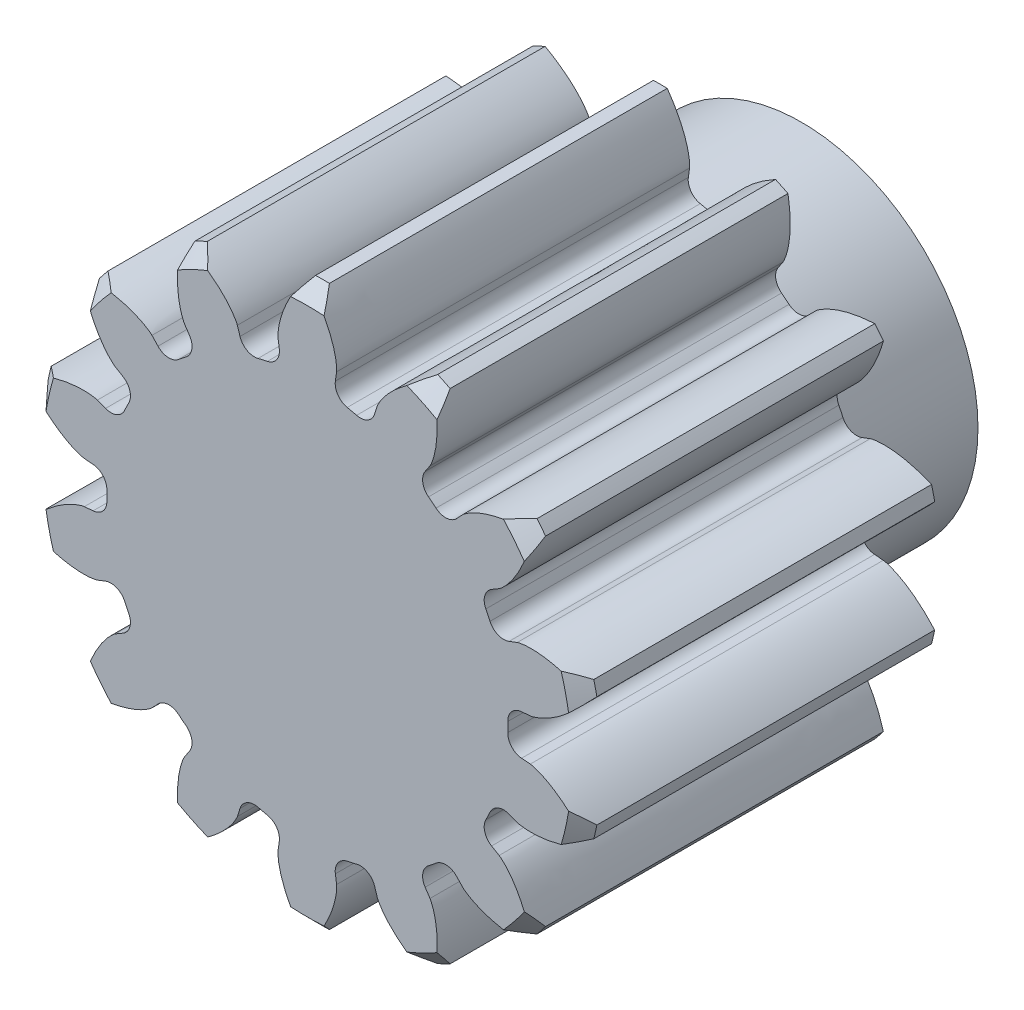
SolidWorks part; units mm, degrees
ref_plane "Front Plane" through (0, 0, 0) normal (0, 0, 1) x (1, 0, 0)
ref_plane "Top Plane" through (0, 0, 0) normal (0, 1, 0) x (1, 0, 0)
ref_plane "Right Plane" through (0, 0, 0) normal (1, 0, 0) x (0, 0, -1)
ref_axis "Axis1" through (0, 0, -5.7505) along (0, 0, 1)
sketch "Sketch1" plane through (0, 0, 0) normal (0, 0, 1) x (1, 0, 0)
  circle A0 centre (0, 0) radius 8
  dimension "D1" = 16
extrude "Boss-Extrude1" add sketch "Sketch1" along normal blind 10
sketch "Sketch2" plane through (0, 0, 10) normal (0, 0, 1) x (1, 0, 0)
  line L0 (0, 0) -> (5.7306, 0.4723) construction
  line L1 (5.7306, 0.4723) -> (6.3227, 0.5211)
  line L2 (0, 0) -> (5.7306, -0.4723) construction
  line L3 (5.7306, -0.4723) -> (6.3227, -0.5211)
  circle A0 centre (0, 0) radius 7 construction
  circle A1 centre (0, 0) radius 8 construction
  circle A2 centre (0, 0) radius 6.3442 construction
  circle A3 centre (0, 0) radius 5.75 construction
  arc A4 (5.7306, 0.4723) -> (5.7306, -0.4723) centre (0, 0) cw
  arc A5 (7.8478, 1.5531) -> (7.8478, -1.5531) centre (0, 0) cw
  spline S0 degree 4 poles (6.3227, 0.5211) (6.3255, 0.5213) (6.3332, 0.5222) (6.3477, 0.5245) (6.3713, 0.5289) (6.4148, 0.5388) (6.4666, 0.5535) (6.5244, 0.5726) (6.5859, 0.5959) (6.638, 0.6174) (6.6895, 0.6403) (6.7403, 0.6645) (6.8014, 0.6954) (6.8738, 0.7346) (6.9573, 0.7836) (7.0504, 0.8428) (7.1436, 0.9071) (7.2338, 0.9734) (7.3232, 1.044) (7.4083, 1.1149) (7.4949, 1.192) (7.5737, 1.265) (7.6598, 1.3506) (7.7285, 1.4209) (7.8167, 1.5175) (7.868, 1.5758) (7.9271, 1.6453) (7.9529, 1.6769) (7.9688, 1.6963) knots 0 0 0 0 0 0.005377 0.015084 0.028532 0.04661 0.092111 0.119476 0.146842 0.174209 0.201575 0.228941 0.256307 0.307035 0.361767 0.4165 0.471232 0.525964 0.580697 0.635429 0.690161 0.744894 0.799626 0.854358 0.909091 0.954545 1 1 1 1 1 construction
  spline S1 degree 4 poles (6.3227, 0.5211) (6.3255, 0.5213) (6.3332, 0.5222) (6.3477, 0.5245) (6.3713, 0.5289) (6.4148, 0.5388) (6.4666, 0.5535) (6.5244, 0.5726) (6.5859, 0.5959) (6.638, 0.6174) (6.6895, 0.6403) (6.7403, 0.6645) (6.8014, 0.6954) (6.8738, 0.7346) (6.9573, 0.7836) (7.0504, 0.8428) (7.1436, 0.9071) (7.2338, 0.9734) (7.3232, 1.044) (7.4083, 1.1149) (7.4949, 1.192) (7.5737, 1.265) (7.6598, 1.3506) (7.7285, 1.4209) (7.7976, 1.4965) (7.8309, 1.5338) (7.8478, 1.5531) knots 0 0 0 0 0 0.005377 0.015084 0.028532 0.04661 0.092111 0.119476 0.146842 0.174209 0.201575 0.228941 0.256307 0.307035 0.361767 0.4165 0.471232 0.525964 0.580697 0.635429 0.690161 0.744894 0.799626 0.854358 0.909091 0.909091 0.909091 0.909091 0.909091
  spline S2 degree 4 poles (6.3227, -0.5211) (6.3255, -0.5213) (6.3332, -0.5222) (6.3477, -0.5245) (6.3713, -0.5289) (6.4148, -0.5388) (6.4666, -0.5535) (6.5244, -0.5726) (6.5859, -0.5959) (6.638, -0.6174) (6.6895, -0.6403) (6.7403, -0.6645) (6.8014, -0.6954) (6.8738, -0.7346) (6.9573, -0.7836) (7.0504, -0.8428) (7.1436, -0.9071) (7.2338, -0.9734) (7.3232, -1.044) (7.4083, -1.1149) (7.4949, -1.192) (7.5737, -1.265) (7.6598, -1.3506) (7.7285, -1.4209) (7.8167, -1.5175) (7.868, -1.5758) (7.9271, -1.6453) (7.9529, -1.6769) (7.9688, -1.6963) knots 0 0 0 0 0 0.005377 0.015084 0.028532 0.04661 0.092111 0.119476 0.146842 0.174209 0.201575 0.228941 0.256307 0.307035 0.361767 0.4165 0.471232 0.525964 0.580697 0.635429 0.690161 0.744894 0.799626 0.854358 0.909091 0.954545 1 1 1 1 1 construction
  spline S3 degree 4 poles (6.3227, -0.5211) (6.3255, -0.5213) (6.3332, -0.5222) (6.3477, -0.5245) (6.3713, -0.5289) (6.4148, -0.5388) (6.4666, -0.5535) (6.5244, -0.5726) (6.5859, -0.5959) (6.638, -0.6174) (6.6895, -0.6403) (6.7403, -0.6645) (6.8014, -0.6954) (6.8738, -0.7346) (6.9573, -0.7836) (7.0504, -0.8428) (7.1436, -0.9071) (7.2338, -0.9734) (7.3232, -1.044) (7.4083, -1.1149) (7.4949, -1.192) (7.5737, -1.265) (7.6598, -1.3506) (7.7285, -1.4209) (7.7976, -1.4965) (7.8309, -1.5338) (7.8478, -1.5531) knots 0 0 0 0 0 0.005377 0.015084 0.028532 0.04661 0.092111 0.119476 0.146842 0.174209 0.201575 0.228941 0.256307 0.307035 0.361767 0.4165 0.471232 0.525964 0.580697 0.635429 0.690161 0.744894 0.799626 0.854358 0.909091 0.909091 0.909091 0.909091 0.909091
  dimension "D1" = 16
  dimension "D2" = 14
  dimension "D3" = 12.6883
  dimension "D4" = 11.5
extrude "Cut-Extrude1" cut sketch "Sketch2" against normal through all
fillet "Fillet1" radius 0.3557 1 edges at (5.7306, 0.4723, 5)
fillet "Fillet2" radius 0.3557 1 edges at (5.7306, -0.4723, 5)
pattern_circular "CirPattern1" count 14 over 360 about axis through (0, 0, 10) along (0, 0, -1) of "Cut-Extrude1", "Fillet1", "Fillet2"
sketch "Sketch4" plane through (0, 0, 10) normal (0, 0, 1) x (1, 0, 0)
  circle A0 centre (0, 0) radius 2
  dimension "D1" = 4
extrude "Bore" cut sketch "Sketch4" against normal through all
sketch "Sketch5" plane through (0, 0, 10) normal (0, 0, 1) x (1, 0, 0)
  line L2 (6.3163, -0.5908) -> (6.0689, -0.5704)
  line L3 (6.3163, -0.5908) -> (6.0689, -0.5704)
  line L4 (6.0689, 0.5704) -> (6.3163, 0.5908)
  line L5 (6.0689, 0.5704) -> (6.3163, 0.5908)
  line L36 (5.9472, 2.2083) -> (5.7154, 2.1193)
  line L37 (5.9472, 2.2083) -> (5.7154, 2.1193)
  line L38 (5.2205, 3.1471) -> (5.4345, 3.2728)
  line L39 (5.2205, 3.1471) -> (5.4345, 3.2728)
  line L40 (4.4001, 4.57) -> (4.2299, 4.3893)
  line L41 (4.4001, 4.57) -> (4.2299, 4.3893)
  line L42 (3.338, 5.1005) -> (3.4763, 5.3067)
  line L43 (3.338, 5.1005) -> (3.4763, 5.3067)
  line L44 (1.9815, 6.0265) -> (1.9065, 5.7899)
  line L45 (1.9815, 6.0265) -> (1.9065, 5.7899)
  line L46 (0.7944, 6.0437) -> (0.8296, 6.2894)
  line L47 (0.7944, 6.0437) -> (0.8296, 6.2894)
  line L48 (-0.8296, 6.2894) -> (-0.7944, 6.0437)
  line L49 (-0.8296, 6.2894) -> (-0.7944, 6.0437)
  line L50 (-1.9065, 5.7899) -> (-1.9815, 6.0265)
  line L51 (-1.9065, 5.7899) -> (-1.9815, 6.0265)
  line L52 (-3.4763, 5.3067) -> (-3.338, 5.1005)
  line L53 (-3.4763, 5.3067) -> (-3.338, 5.1005)
  line L54 (-4.2299, 4.3893) -> (-4.4001, 4.57)
  line L55 (-4.2299, 4.3893) -> (-4.4001, 4.57)
  line L56 (-5.4345, 3.2728) -> (-5.2205, 3.1471)
  line L57 (-5.4345, 3.2728) -> (-5.2205, 3.1471)
  line L58 (-5.7154, 2.1193) -> (-5.9472, 2.2083)
  line L59 (-5.7154, 2.1193) -> (-5.9472, 2.2083)
  line L60 (-6.3163, 0.5908) -> (-6.0689, 0.5704)
  line L61 (-6.3163, 0.5908) -> (-6.0689, 0.5704)
  line L62 (-6.0689, -0.5704) -> (-6.3163, -0.5908)
  line L63 (-6.0689, -0.5704) -> (-6.3163, -0.5908)
  line L64 (-5.9472, -2.2083) -> (-5.7154, -2.1193)
  line L65 (-5.9472, -2.2083) -> (-5.7154, -2.1193)
  line L66 (-5.2205, -3.1471) -> (-5.4345, -3.2728)
  line L67 (-5.2205, -3.1471) -> (-5.4345, -3.2728)
  line L68 (-4.4001, -4.57) -> (-4.2299, -4.3893)
  line L69 (-4.4001, -4.57) -> (-4.2299, -4.3893)
  line L70 (-3.338, -5.1005) -> (-3.4763, -5.3067)
  line L71 (-3.338, -5.1005) -> (-3.4763, -5.3067)
  line L72 (-1.9815, -6.0265) -> (-1.9065, -5.7899)
  line L73 (-1.9815, -6.0265) -> (-1.9065, -5.7899)
  line L74 (-0.7944, -6.0437) -> (-0.8296, -6.2894)
  line L75 (-0.7944, -6.0437) -> (-0.8296, -6.2894)
  line L76 (0.8296, -6.2894) -> (0.7944, -6.0437)
  line L77 (0.8296, -6.2894) -> (0.7944, -6.0437)
  line L78 (1.9065, -5.7899) -> (1.9815, -6.0265)
  line L79 (1.9065, -5.7899) -> (1.9815, -6.0265)
  line L80 (3.4763, -5.3067) -> (3.338, -5.1005)
  line L81 (3.4763, -5.3067) -> (3.338, -5.1005)
  line L82 (4.2299, -4.3893) -> (4.4001, -4.57)
  line L83 (4.2299, -4.3893) -> (4.4001, -4.57)
  line L84 (5.4345, -3.2728) -> (5.2205, -3.1471)
  line L85 (5.4345, -3.2728) -> (5.2205, -3.1471)
  line L86 (5.7154, -2.1193) -> (5.9472, -2.2083)
  line L87 (5.7154, -2.1193) -> (5.9472, -2.2083)
  arc A2 (5.6784, -0.136) -> (5.6784, 0.136) centre (0, 0) ccw
  arc A3 (5.6784, -0.136) -> (5.6784, 0.136) centre (0, 0) ccw
  arc A56 (7.7723, 1.5734) -> (7.6853, 1.9547) centre (0, 0) ccw
  arc A57 (7.7723, 1.5734) -> (7.6853, 1.9547) centre (0, 0) ccw
  arc A62 (5.175, 2.3412) -> (5.7154, 2.1193) centre (5.5628, 2.5167) ccw
  arc A64 (5.175, 2.3412) -> (5.7154, 2.1193) centre (5.5628, 2.5167) ccw
  arc A66 (5.175, 2.3412) -> (5.057, 2.5863) centre (0, 0) ccw
  arc A68 (5.175, 2.3412) -> (5.057, 2.5863) centre (0, 0) ccw
  arc A70 (5.2205, 3.1471) -> (5.057, 2.5863) centre (5.436, 2.7801) ccw
  arc A72 (5.2205, 3.1471) -> (5.057, 2.5863) centre (5.436, 2.7801) ccw
  arc A73 (6.3199, 4.7899) -> (6.0761, 5.0956) centre (0, 0) ccw
  arc A74 (6.3199, 4.7899) -> (6.0761, 5.0956) centre (0, 0) ccw
  arc A75 (3.6467, 4.3548) -> (4.2299, 4.3893) centre (3.92, 4.6811) ccw
  arc A76 (3.6467, 4.3548) -> (4.2299, 4.3893) centre (3.92, 4.6811) ccw
  arc A77 (3.6467, 4.3548) -> (3.4341, 4.5243) centre (0, 0) ccw
  arc A78 (3.6467, 4.3548) -> (3.4341, 4.5243) centre (0, 0) ccw
  arc A79 (3.338, 5.1005) -> (3.4341, 4.5243) centre (3.6914, 4.8634) ccw
  arc A80 (3.338, 5.1005) -> (3.4341, 4.5243) centre (3.6914, 4.8634) ccw
  arc A81 (3.6158, 7.0577) -> (3.2635, 7.2273) centre (0, 0) ccw
  arc A82 (3.6158, 7.0577) -> (3.2635, 7.2273) centre (0, 0) ccw
  arc A83 (1.3961, 5.5057) -> (1.9065, 5.7899) centre (1.5007, 5.9183) ccw
  arc A84 (1.3961, 5.5057) -> (1.9065, 5.7899) centre (1.5007, 5.9183) ccw
  arc A85 (1.3961, 5.5057) -> (1.131, 5.5663) centre (0, 0) ccw
  arc A86 (1.3961, 5.5057) -> (1.131, 5.5663) centre (0, 0) ccw
  arc A87 (0.7944, 6.0437) -> (1.131, 5.5663) centre (1.2157, 5.9834) ccw
  arc A88 (0.7944, 6.0437) -> (1.131, 5.5663) centre (1.2157, 5.9834) ccw
  arc A89 (0.1955, 7.9276) -> (-0.1955, 7.9276) centre (0, 0) ccw
  arc A90 (0.1955, 7.9276) -> (-0.1955, 7.9276) centre (0, 0) ccw
  arc A91 (-1.131, 5.5663) -> (-0.7944, 6.0437) centre (-1.2157, 5.9834) ccw
  arc A92 (-1.131, 5.5663) -> (-0.7944, 6.0437) centre (-1.2157, 5.9834) ccw
  arc A93 (-1.131, 5.5663) -> (-1.3961, 5.5057) centre (0, 0) ccw
  arc A94 (-1.131, 5.5663) -> (-1.3961, 5.5057) centre (0, 0) ccw
  arc A95 (-1.9065, 5.7899) -> (-1.3961, 5.5057) centre (-1.5007, 5.9183) ccw
  arc A96 (-1.9065, 5.7899) -> (-1.3961, 5.5057) centre (-1.5007, 5.9183) ccw
  arc A97 (-3.2635, 7.2273) -> (-3.6158, 7.0577) centre (0, 0) ccw
  arc A98 (-3.2635, 7.2273) -> (-3.6158, 7.0577) centre (0, 0) ccw
  arc A99 (-3.4341, 4.5243) -> (-3.338, 5.1005) centre (-3.6914, 4.8634) ccw
  arc A100 (-3.4341, 4.5243) -> (-3.338, 5.1005) centre (-3.6914, 4.8634) ccw
  arc A101 (-3.4341, 4.5243) -> (-3.6467, 4.3548) centre (0, 0) ccw
  arc A102 (-3.4341, 4.5243) -> (-3.6467, 4.3548) centre (0, 0) ccw
  arc A103 (-4.2299, 4.3893) -> (-3.6467, 4.3548) centre (-3.92, 4.6811) ccw
  arc A104 (-4.2299, 4.3893) -> (-3.6467, 4.3548) centre (-3.92, 4.6811) ccw
  arc A105 (-6.0761, 5.0956) -> (-6.3199, 4.7899) centre (0, 0) ccw
  arc A106 (-6.0761, 5.0956) -> (-6.3199, 4.7899) centre (0, 0) ccw
  arc A107 (-5.057, 2.5863) -> (-5.2205, 3.1471) centre (-5.436, 2.7801) ccw
  arc A108 (-5.057, 2.5863) -> (-5.2205, 3.1471) centre (-5.436, 2.7801) ccw
  arc A109 (-5.057, 2.5863) -> (-5.175, 2.3412) centre (0, 0) ccw
  arc A110 (-5.057, 2.5863) -> (-5.175, 2.3412) centre (0, 0) ccw
  arc A111 (-5.7154, 2.1193) -> (-5.175, 2.3412) centre (-5.5628, 2.5167) ccw
  arc A112 (-5.7154, 2.1193) -> (-5.175, 2.3412) centre (-5.5628, 2.5167) ccw
  arc A113 (-7.6853, 1.9547) -> (-7.7723, 1.5734) centre (0, 0) ccw
  arc A114 (-7.6853, 1.9547) -> (-7.7723, 1.5734) centre (0, 0) ccw
  arc A115 (-5.6784, 0.136) -> (-6.0689, 0.5704) centre (-6.1039, 0.1462) ccw
  arc A116 (-5.6784, 0.136) -> (-6.0689, 0.5704) centre (-6.1039, 0.1462) ccw
  arc A117 (-5.6784, 0.136) -> (-5.6784, -0.136) centre (0, 0) ccw
  arc A118 (-5.6784, 0.136) -> (-5.6784, -0.136) centre (0, 0) ccw
  arc A119 (-6.0689, -0.5704) -> (-5.6784, -0.136) centre (-6.1039, -0.1462) ccw
  arc A120 (-6.0689, -0.5704) -> (-5.6784, -0.136) centre (-6.1039, -0.1462) ccw
  arc A121 (-7.7723, -1.5734) -> (-7.6853, -1.9547) centre (0, 0) ccw
  arc A122 (-7.7723, -1.5734) -> (-7.6853, -1.9547) centre (0, 0) ccw
  arc A123 (-5.175, -2.3412) -> (-5.7154, -2.1193) centre (-5.5628, -2.5167) ccw
  arc A124 (-5.175, -2.3412) -> (-5.7154, -2.1193) centre (-5.5628, -2.5167) ccw
  arc A125 (-5.175, -2.3412) -> (-5.057, -2.5863) centre (0, 0) ccw
  arc A126 (-5.175, -2.3412) -> (-5.057, -2.5863) centre (0, 0) ccw
  arc A127 (-5.2205, -3.1471) -> (-5.057, -2.5863) centre (-5.436, -2.7801) ccw
  arc A128 (-5.2205, -3.1471) -> (-5.057, -2.5863) centre (-5.436, -2.7801) ccw
  arc A129 (-6.3199, -4.7899) -> (-6.0761, -5.0956) centre (0, 0) ccw
  arc A130 (-6.3199, -4.7899) -> (-6.0761, -5.0956) centre (0, 0) ccw
  arc A131 (-3.6467, -4.3548) -> (-4.2299, -4.3893) centre (-3.92, -4.6811) ccw
  arc A132 (-3.6467, -4.3548) -> (-4.2299, -4.3893) centre (-3.92, -4.6811) ccw
  arc A133 (-3.6467, -4.3548) -> (-3.4341, -4.5243) centre (0, 0) ccw
  arc A134 (-3.6467, -4.3548) -> (-3.4341, -4.5243) centre (0, 0) ccw
  arc A135 (-3.338, -5.1005) -> (-3.4341, -4.5243) centre (-3.6914, -4.8634) ccw
  arc A136 (-3.338, -5.1005) -> (-3.4341, -4.5243) centre (-3.6914, -4.8634) ccw
  arc A137 (-3.6158, -7.0577) -> (-3.2635, -7.2273) centre (0, 0) ccw
  arc A138 (-3.6158, -7.0577) -> (-3.2635, -7.2273) centre (0, 0) ccw
  arc A139 (-1.3961, -5.5057) -> (-1.9065, -5.7899) centre (-1.5007, -5.9183) ccw
  arc A140 (-1.3961, -5.5057) -> (-1.9065, -5.7899) centre (-1.5007, -5.9183) ccw
  arc A141 (-1.3961, -5.5057) -> (-1.131, -5.5663) centre (0, 0) ccw
  arc A142 (-1.3961, -5.5057) -> (-1.131, -5.5663) centre (0, 0) ccw
  arc A143 (-0.7944, -6.0437) -> (-1.131, -5.5663) centre (-1.2157, -5.9834) ccw
  circle A144 centre (0, 0) radius 16
  arc A145 (-0.7944, -6.0437) -> (-1.131, -5.5663) centre (-1.2157, -5.9834) ccw
  arc A146 (-0.1955, -7.9276) -> (0.1955, -7.9276) centre (0, 0) ccw
  arc A147 (-0.1955, -7.9276) -> (0.1955, -7.9276) centre (0, 0) ccw
  arc A148 (1.131, -5.5663) -> (0.7944, -6.0437) centre (1.2157, -5.9834) ccw
  arc A149 (1.131, -5.5663) -> (0.7944, -6.0437) centre (1.2157, -5.9834) ccw
  arc A150 (1.131, -5.5663) -> (1.3961, -5.5057) centre (0, 0) ccw
  arc A151 (1.131, -5.5663) -> (1.3961, -5.5057) centre (0, 0) ccw
  arc A152 (1.9065, -5.7899) -> (1.3961, -5.5057) centre (1.5007, -5.9183) ccw
  arc A153 (1.9065, -5.7899) -> (1.3961, -5.5057) centre (1.5007, -5.9183) ccw
  arc A154 (3.2635, -7.2273) -> (3.6158, -7.0577) centre (0, 0) ccw
  arc A155 (3.2635, -7.2273) -> (3.6158, -7.0577) centre (0, 0) ccw
  arc A156 (3.4341, -4.5243) -> (3.338, -5.1005) centre (3.6914, -4.8634) ccw
  arc A157 (3.4341, -4.5243) -> (3.338, -5.1005) centre (3.6914, -4.8634) ccw
  arc A158 (3.4341, -4.5243) -> (3.6467, -4.3548) centre (0, 0) ccw
  arc A159 (3.4341, -4.5243) -> (3.6467, -4.3548) centre (0, 0) ccw
  arc A160 (4.2299, -4.3893) -> (3.6467, -4.3548) centre (3.92, -4.6811) ccw
  arc A161 (4.2299, -4.3893) -> (3.6467, -4.3548) centre (3.92, -4.6811) ccw
  arc A162 (6.0761, -5.0956) -> (6.3199, -4.7899) centre (0, 0) ccw
  arc A163 (6.0761, -5.0956) -> (6.3199, -4.7899) centre (0, 0) ccw
  arc A164 (5.057, -2.5863) -> (5.2205, -3.1471) centre (5.436, -2.7801) ccw
  arc A165 (5.057, -2.5863) -> (5.2205, -3.1471) centre (5.436, -2.7801) ccw
  arc A166 (5.057, -2.5863) -> (5.175, -2.3412) centre (0, 0) ccw
  arc A167 (5.057, -2.5863) -> (5.175, -2.3412) centre (0, 0) ccw
  arc A168 (5.7154, -2.1193) -> (5.175, -2.3412) centre (5.5628, -2.5167) ccw
  arc A169 (5.7154, -2.1193) -> (5.175, -2.3412) centre (5.5628, -2.5167) ccw
  arc A170 (7.6853, -1.9547) -> (7.7723, -1.5734) centre (0, 0) ccw
  arc A171 (7.6853, -1.9547) -> (7.7723, -1.5734) centre (0, 0) ccw
  arc A172 (5.6784, -0.136) -> (6.0689, -0.5704) centre (6.1039, -0.1462) ccw
  arc A173 (5.6784, -0.136) -> (6.0689, -0.5704) centre (6.1039, -0.1462) ccw
  arc A174 (6.0689, 0.5704) -> (5.6784, 0.136) centre (6.1039, 0.1462) ccw
  arc A175 (6.0689, 0.5704) -> (5.6784, 0.136) centre (6.1039, 0.1462) ccw
  spline S2 degree 3 poles (544.5937, 1924.9705) (-39.0958, -115.8227) (20.5489, -10.6302) (6.9943, -0.8868) (6.8676, -0.8075) (6.6687, -0.7068) (6.5673, -0.6612) (6.4617, -0.6254) (3.9438, 0.1017) (0.0048, -0.5372) (-301.8823, -1976.3791) knots -27.332414 -27.332414 -27.332414 -27.332414 0.5 0.5 0.75 0.75 0.875 0.9375 0.9375 5.261207 5.261207 5.261207 5.261207 only from (7.7723, -1.5734) to (6.3163, -0.5908)
  spline S3 degree 3 poles (7.7723, -1.5734) (7.574, -1.3513) (7.3563, -1.147) (6.9943, -0.8868) (6.8676, -0.8075) (6.6687, -0.7068) (6.5673, -0.6612) (6.4617, -0.6254) (6.3899, -0.6047) (6.3537, -0.5946) (6.3163, -0.5908) knots 0 0 0 0 0.5 0.5 0.75 0.75 0.875 0.9375 0.9375 1 1 1 1
  spline S4 degree 3 poles (-572.3729, 1914.8313) (1.1127, 0.5156) (3.9663, -0.0954) (6.4618, 0.6254) (6.4971, 0.6374) (6.6022, 0.6769) (6.6705, 0.7077) (6.869, 0.8083) (6.9942, 0.8868) (19.9003, 10.1603) (-27.7396, 111.2518) (-4.3909, -1998.173) knots -4.22541 -4.22541 -4.22541 -4.22541 0.0625 0.0625 0.125 0.125 0.25 0.25 0.5 0.5 27.094951 27.094951 27.094951 27.094951 only from (6.3163, 0.5908) to (7.7723, 1.5734)
  spline S5 degree 3 poles (6.3163, 0.5908) (6.3541, 0.5946) (6.3901, 0.6047) (6.4618, 0.6254) (6.4971, 0.6374) (6.6022, 0.6769) (6.6705, 0.7077) (6.869, 0.8083) (6.9942, 0.8868) (7.3548, 1.1458) (7.5738, 1.3511) (7.7723, 1.5734) knots 0 0 0 0 0.0625 0.0625 0.125 0.125 0.25 0.25 0.5 0.5 1 1 1 1
  spline S32 degree 3 poles (-172.5124, 985.5849) (17.2536, -78.9181) (19.9638, -0.1043) (6.6864, 2.2357) (6.5379, 2.2522) (6.315, 2.2566) (6.2038, 2.2537) (6.0931, 2.2401) (4.0348, 1.8917) (1.5571, 0.3822) (293.1672, -955.476) knots -21.930557 -21.930557 -21.930557 -21.930557 0.5 0.5 0.75 0.75 0.875 0.9375 0.9375 4.368835 4.368835 4.368835 4.368835 only from (7.6853, 1.9547) to (5.9472, 2.2083)
  spline S33 degree 3 poles (7.6853, 1.9547) (7.4103, 2.0688) (7.1254, 2.1584) (6.6864, 2.2357) (6.5379, 2.2522) (6.315, 2.2566) (6.2038, 2.2537) (6.0931, 2.2401) (6.0195, 2.2277) (5.9825, 2.2211) (5.9472, 2.2083) knots 0 0 0 0 0.5 0.5 0.75 0.75 0.875 0.9375 0.9375 1 1 1 1
  spline S34 degree 3 poles (-672.2193, 738.6505) (1.9101, 1.2746) (4.0087, 1.9874) (5.5505, 3.3671) (5.5771, 3.3933) (5.6547, 3.4744) (5.7029, 3.5318) (5.8381, 3.7086) (5.9168, 3.8336) (12.0502, 15.0892) (-42.9692, 62.8605) (423.2789, -904.1314) knots -3.340287 -3.340287 -3.340287 -3.340287 0.0625 0.0625 0.125 0.125 0.25 0.25 0.5 0.5 21.902267 21.902267 21.902267 21.902267 only from (5.4345, 3.2728) to (6.3199, 4.7899)
  spline S35 degree 3 poles (5.4345, 3.2728) (5.4669, 3.2927) (5.4949, 3.3174) (5.5505, 3.3671) (5.5771, 3.3933) (5.6547, 3.4744) (5.7029, 3.5318) (5.8381, 3.7086) (5.9168, 3.8336) (6.1293, 4.2235) (6.2376, 4.5034) (6.3199, 4.7899) knots 0 0 0 0 0.0625 0.0625 0.125 0.125 0.25 0.25 0.5 0.5 1 1 1 1
  spline S36 degree 3 poles (-583.0575, 813.131) (49.7862, -63.6167) (18.0321, 8.568) (5.0542, 4.9154) (4.9132, 4.8659) (4.7105, 4.7731) (4.6116, 4.7223) (4.5177, 4.662) (2.8145, 3.455) (1.237, 1.0199) (678.7, -733.6536) knots -21.930557 -21.930557 -21.930557 -21.930557 0.5 0.5 0.75 0.75 0.875 0.9375 0.9375 4.368835 4.368835 4.368835 4.368835 only from (6.0761, 5.0956) to (4.4001, 4.57)
  spline S37 degree 3 poles (6.0761, 5.0956) (5.7788, 5.0791) (5.4833, 5.0362) (5.0542, 4.9154) (4.9132, 4.8659) (4.7105, 4.7731) (4.6116, 4.7223) (4.5177, 4.662) (4.4568, 4.6188) (4.4264, 4.5968) (4.4001, 4.57) knots 0 0 0 0 0.5 0.5 0.75 0.75 0.875 0.9375 0.9375 1 1 1 1
  spline S38 degree 3 poles (-926.1371, 373.8361) (1.1679, 1.9772) (2.7495, 3.5299) (3.5399, 5.442) (3.5525, 5.4771) (3.5872, 5.5838) (3.6057, 5.6565) (3.6508, 5.8744) (3.6675, 6.0212) (4.3099, 18.8233) (-65.9881, 37.9917) (773.6491, -630.9405) knots -3.340287 -3.340287 -3.340287 -3.340287 0.0625 0.0625 0.125 0.125 0.25 0.25 0.5 0.5 21.902267 21.902267 21.902267 21.902267 only from (3.4763, 5.3067) to (3.6158, 7.0577)
  spline S39 degree 3 poles (3.4763, 5.3067) (3.4968, 5.3386) (3.5114, 5.373) (3.5399, 5.442) (3.5525, 5.4771) (3.5872, 5.5838) (3.6057, 5.6565) (3.6508, 5.8744) (3.6675, 6.0212) (3.6898, 6.4646) (3.6659, 6.7638) (3.6158, 7.0577) knots 0 0 0 0 0.0625 0.0625 0.125 0.125 0.25 0.25 0.5 0.5 1 1 1 1
  spline S40 degree 3 poles (-878.121, 479.6266) (72.4581, -35.7152) (12.5288, 15.5433) (2.4209, 6.6216) (2.3154, 6.5158) (2.1731, 6.3443) (2.106, 6.2555) (2.0476, 6.1605) (1.0367, 4.334) (0.672, 1.4556) (929.8079, -366.5222) knots -21.930557 -21.930557 -21.930557 -21.930557 0.5 0.5 0.75 0.75 0.875 0.9375 0.9375 4.368835 4.368835 4.368835 4.368835 only from (3.2635, 7.2273) to (1.9815, 6.0265)
  spline S41 degree 3 poles (3.2635, 7.2273) (3.0028, 7.0834) (2.7552, 6.9166) (2.4209, 6.6216) (2.3154, 6.5158) (2.1731, 6.3443) (2.106, 6.2555) (2.0476, 6.1605) (2.0114, 6.0951) (1.9935, 6.0621) (1.9815, 6.0265) knots 0 0 0 0 0.5 0.5 0.75 0.75 0.875 0.9375 0.9375 1 1 1 1
  spline S42 degree 3 poles (-996.6221, -65.0212) (0.1944, 2.2881) (0.9456, 4.3733) (0.8281, 6.4389) (0.8243, 6.4761) (0.8092, 6.5873) (0.7944, 6.6608) (0.7405, 6.8767) (0.6918, 7.0162) (-4.284, 18.8292) (-75.9372, 5.5982) (970.7885, -232.784) knots -3.340287 -3.340287 -3.340287 -3.340287 0.0625 0.0625 0.125 0.125 0.25 0.25 0.5 0.5 21.902267 21.902267 21.902267 21.902267 only from (0.8296, 6.2894) to (0.1955, 7.9276)
  spline S43 degree 3 poles (0.8296, 6.2894) (0.8342, 6.3271) (0.8324, 6.3644) (0.8281, 6.4389) (0.8243, 6.4761) (0.8092, 6.5873) (0.7944, 6.6608) (0.7405, 6.8767) (0.6918, 7.0162) (0.5195, 7.4253) (0.3681, 7.6845) (0.1955, 7.9276) knots 0 0 0 0 0.0625 0.0625 0.125 0.125 0.25 0.25 0.5 0.5 1 1 1 1
  spline S44 degree 3 poles (-999.2619, 51.1262) (80.7788, -0.7399) (4.5441, 19.4401) (-0.6918, 7.0162) (-0.741, 6.8751) (-0.7948, 6.6588) (-0.8167, 6.5498) (-0.8281, 6.4388) (-0.9465, 4.3546) (-0.0261, 1.6031) (996.756, 73.2035) knots -21.930557 -21.930557 -21.930557 -21.930557 0.5 0.5 0.75 0.75 0.875 0.9375 0.9375 4.368835 4.368835 4.368835 4.368835 only from (-0.1955, 7.9276) to (-0.8296, 6.2894)
  spline S45 degree 3 poles (-0.1955, 7.9276) (-0.368, 7.6848) (-0.5187, 7.4271) (-0.6918, 7.0162) (-0.741, 6.8751) (-0.7948, 6.6588) (-0.8167, 6.5498) (-0.8281, 6.4388) (-0.8324, 6.3643) (-0.8341, 6.3267) (-0.8296, 6.2894) knots 0 0 0 0 0.5 0.5 0.75 0.75 0.875 0.9375 0.9375 1 1 1 1
  spline S46 degree 3 poles (-869.7138, -491.0001) (-0.8176, 2.1458) (-1.0455, 4.3505) (-2.0476, 6.1606) (-2.0672, 6.1924) (-2.129, 6.286) (-2.1743, 6.3458) (-2.3165, 6.5169) (-2.4209, 6.6215) (-12.0294, 15.1058) (-70.8461, -27.9041) (975.6514, 211.4782) knots -3.340287 -3.340287 -3.340287 -3.340287 0.0625 0.0625 0.125 0.125 0.25 0.25 0.5 0.5 21.902267 21.902267 21.902267 21.902267 only from (-1.9815, 6.0265) to (-3.2635, 7.2273)
  spline S47 degree 3 poles (-1.9815, 6.0265) (-1.9937, 6.0625) (-2.0115, 6.0953) (-2.0476, 6.1606) (-2.0672, 6.1924) (-2.129, 6.286) (-2.1743, 6.3458) (-2.3165, 6.5169) (-2.4209, 6.6215) (-2.7537, 6.9154) (-3.0025, 7.0833) (-3.2635, 7.2273) knots 0 0 0 0 0.0625 0.0625 0.125 0.125 0.25 0.25 0.5 0.5 1 1 1 1
  spline S48 degree 3 poles (-922.4866, -387.5004) (73.1002, 34.382) (-4.3407, 19.4865) (-3.6675, 6.0212) (-3.6506, 5.8728) (-3.6053, 5.6545) (-3.5777, 5.5468) (-3.5398, 5.4419) (-2.7421, 3.5127) (-0.7191, 1.433) (866.2843, 498.4303) knots -21.930557 -21.930557 -21.930557 -21.930557 0.5 0.5 0.75 0.75 0.875 0.9375 0.9375 4.368835 4.368835 4.368835 4.368835 only from (-3.6158, 7.0577) to (-3.4763, 5.3067)
  spline S49 degree 3 poles (-3.6158, 7.0577) (-3.6658, 6.7641) (-3.6898, 6.4665) (-3.6675, 6.0212) (-3.6506, 5.8728) (-3.6053, 5.6545) (-3.5777, 5.5468) (-3.5398, 5.4419) (-3.5113, 5.3728) (-3.4966, 5.3383) (-3.4763, 5.3067) knots 0 0 0 0 0.5 0.5 0.75 0.75 0.875 0.9375 0.9375 1 1 1 1
  spline S50 degree 3 poles (-570.5481, -819.7305) (-1.6677, 1.5786) (-2.8296, 3.466) (-4.5178, 4.6621) (-4.5492, 4.6822) (-4.6456, 4.7398) (-4.7123, 4.774) (-4.9147, 4.8665) (-5.0541, 4.9154) (-17.3923, 8.3904) (-51.7229, -55.8797) (787.2746, 613.8546) knots -3.340287 -3.340287 -3.340287 -3.340287 0.0625 0.0625 0.125 0.125 0.25 0.25 0.5 0.5 21.902267 21.902267 21.902267 21.902267 only from (-4.4001, 4.57) to (-6.0761, 5.0956)
  spline S51 degree 3 poles (-4.4001, 4.57) (-4.4266, 4.5971) (-4.4569, 4.6189) (-4.5178, 4.6621) (-4.5492, 4.6822) (-4.6456, 4.7398) (-4.7123, 4.774) (-4.9147, 4.8665) (-5.0541, 4.9154) (-5.4815, 5.0358) (-5.7785, 5.0791) (-6.0761, 5.0956) knots 0 0 0 0 0.0625 0.0625 0.125 0.125 0.25 0.25 0.5 0.5 1 1 1 1
  spline S52 degree 3 poles (-663.0016, -749.3777) (50.9432, 62.694) (-12.3657, 15.6734) (-5.9169, 3.8336) (-5.8372, 3.7073) (-5.7016, 3.5303) (-5.63, 3.4452) (-5.5504, 3.3671) (-3.9947, 1.9751) (-1.2696, 0.9791) (564.2344, 824.9369) knots -21.930557 -21.930557 -21.930557 -21.930557 0.5 0.5 0.75 0.75 0.875 0.9375 0.9375 4.368835 4.368835 4.368835 4.368835 only from (-6.3199, 4.7899) to (-5.4345, 3.2728)
  spline S53 degree 3 poles (-6.3199, 4.7899) (-6.2376, 4.5037) (-6.1301, 4.2252) (-5.9169, 3.8336) (-5.8372, 3.7073) (-5.7016, 3.5303) (-5.63, 3.4452) (-5.5504, 3.3671) (-5.4948, 3.3173) (-5.4665, 3.2925) (-5.4345, 3.2728) knots 0 0 0 0 0.5 0.5 0.75 0.75 0.875 0.9375 0.9375 1 1 1 1
  spline S54 degree 3 poles (-158.3783, -986.1032) (-2.1875, 0.6987) (-4.0532, 1.8951) (-6.0932, 2.2402) (-6.1303, 2.2447) (-6.242, 2.2548) (-6.317, 2.2566) (-6.5395, 2.2521) (-6.6863, 2.2357) (-19.3104, 0.0133) (-22.3555, -72.7876) (442.9683, 894.6495) knots -3.340287 -3.340287 -3.340287 -3.340287 0.0625 0.0625 0.125 0.125 0.25 0.25 0.5 0.5 21.902267 21.902267 21.902267 21.902267 only from (-5.9472, 2.2083) to (-7.6853, 1.9547)
  spline S55 degree 3 poles (-5.9472, 2.2083) (-5.9829, 2.2212) (-6.0196, 2.2277) (-6.0932, 2.2402) (-6.1303, 2.2447) (-6.242, 2.2548) (-6.317, 2.2566) (-6.5395, 2.2521) (-6.6863, 2.2357) (-7.1236, 2.1587) (-7.41, 2.0689) (-7.6853, 1.9547) knots 0 0 0 0 0.0625 0.0625 0.125 0.125 0.25 0.25 0.5 0.5 1 1 1 1
  spline S56 degree 3 poles (-272.201, -962.8316) (18.6963, 78.5888) (-17.9415, 8.756) (-6.9943, 0.8868) (-6.8676, 0.8075) (-6.6687, 0.7068) (-6.5673, 0.6612) (-6.4617, 0.6254) (-4.456, 0.0463) (-1.5687, 0.3312) (150.431, 988.0546) knots -21.930557 -21.930557 -21.930557 -21.930557 0.5 0.5 0.75 0.75 0.875 0.9375 0.9375 4.368835 4.368835 4.368835 4.368835 only from (-7.7723, 1.5734) to (-6.3163, 0.5908)
  spline S57 degree 3 poles (-7.7723, 1.5734) (-7.574, 1.3513) (-7.3563, 1.147) (-6.9943, 0.8868) (-6.8676, 0.8075) (-6.6687, 0.7068) (-6.5673, 0.6612) (-6.4617, 0.6254) (-6.3899, 0.6047) (-6.3537, 0.5946) (-6.3163, 0.5908) knots 0 0 0 0 0.5 0.5 0.75 0.75 0.875 0.9375 0.9375 1 1 1 1
  spline S58 degree 3 poles (285.1602, -957.1661) (-2.274, -0.3196) (-4.474, -0.0512) (-6.4618, -0.6254) (-6.4971, -0.6374) (-6.6022, -0.6769) (-6.6705, -0.7077) (-6.869, -0.8083) (-6.9942, -0.8868) (-17.4038, -8.3665) (11.4398, -75.279) (10.9268, 998.2481) knots -3.340287 -3.340287 -3.340287 -3.340287 0.0625 0.0625 0.125 0.125 0.25 0.25 0.5 0.5 21.902267 21.902267 21.902267 21.902267 only from (-6.3163, -0.5908) to (-7.7723, -1.5734)
  spline S59 degree 3 poles (-6.3163, -0.5908) (-6.3541, -0.5946) (-6.3901, -0.6047) (-6.4618, -0.6254) (-6.4971, -0.6374) (-6.6022, -0.6769) (-6.6705, -0.7077) (-6.869, -0.8083) (-6.9942, -0.8868) (-7.3548, -1.1458) (-7.5738, -1.3511) (-7.7723, -1.5734) knots 0 0 0 0 0.0625 0.0625 0.125 0.125 0.25 0.25 0.5 0.5 1 1 1 1
  spline S60 degree 3 poles (172.5124, -985.5849) (-17.2536, 78.9181) (-19.9638, 0.1043) (-6.6864, -2.2357) (-6.5379, -2.2522) (-6.315, -2.2566) (-6.2038, -2.2537) (-6.0931, -2.2401) (-4.0348, -1.8917) (-1.5571, -0.3822) (-293.1672, 955.476) knots -21.930557 -21.930557 -21.930557 -21.930557 0.5 0.5 0.75 0.75 0.875 0.9375 0.9375 4.368835 4.368835 4.368835 4.368835 only from (-7.6853, -1.9547) to (-5.9472, -2.2083)
  spline S61 degree 3 poles (-7.6853, -1.9547) (-7.4103, -2.0688) (-7.1254, -2.1584) (-6.6864, -2.2357) (-6.5379, -2.2522) (-6.315, -2.2566) (-6.2038, -2.2537) (-6.0931, -2.2401) (-6.0195, -2.2277) (-5.9825, -2.2211) (-5.9472, -2.2083) knots 0 0 0 0 0.5 0.5 0.75 0.75 0.875 0.9375 0.9375 1 1 1 1
  spline S62 degree 3 poles (672.2193, -738.6505) (-1.9101, -1.2746) (-4.0087, -1.9874) (-5.5505, -3.3671) (-5.5771, -3.3933) (-5.6547, -3.4744) (-5.7029, -3.5318) (-5.8381, -3.7086) (-5.9168, -3.8336) (-12.0502, -15.0892) (42.9692, -62.8605) (-423.2789, 904.1314) knots -3.340287 -3.340287 -3.340287 -3.340287 0.0625 0.0625 0.125 0.125 0.25 0.25 0.5 0.5 21.902267 21.902267 21.902267 21.902267 only from (-5.4345, -3.2728) to (-6.3199, -4.7899)
  spline S63 degree 3 poles (-5.4345, -3.2728) (-5.4669, -3.2927) (-5.4949, -3.3174) (-5.5505, -3.3671) (-5.5771, -3.3933) (-5.6547, -3.4744) (-5.7029, -3.5318) (-5.8381, -3.7086) (-5.9168, -3.8336) (-6.1293, -4.2235) (-6.2376, -4.5034) (-6.3199, -4.7899) knots 0 0 0 0 0.0625 0.0625 0.125 0.125 0.25 0.25 0.5 0.5 1 1 1 1
  spline S64 degree 3 poles (583.0575, -813.131) (-49.7862, 63.6167) (-18.0321, -8.568) (-5.0542, -4.9154) (-4.9132, -4.8659) (-4.7105, -4.7731) (-4.6116, -4.7223) (-4.5177, -4.662) (-2.8145, -3.455) (-1.237, -1.0199) (-678.7, 733.6536) knots -21.930557 -21.930557 -21.930557 -21.930557 0.5 0.5 0.75 0.75 0.875 0.9375 0.9375 4.368835 4.368835 4.368835 4.368835 only from (-6.0761, -5.0956) to (-4.4001, -4.57)
  spline S65 degree 3 poles (-6.0761, -5.0956) (-5.7788, -5.0791) (-5.4833, -5.0362) (-5.0542, -4.9154) (-4.9132, -4.8659) (-4.7105, -4.7731) (-4.6116, -4.7223) (-4.5177, -4.662) (-4.4568, -4.6188) (-4.4264, -4.5968) (-4.4001, -4.57) knots 0 0 0 0 0.5 0.5 0.75 0.75 0.875 0.9375 0.9375 1 1 1 1
  spline S66 degree 3 poles (926.1371, -373.8361) (-1.1679, -1.9772) (-2.7495, -3.5299) (-3.5399, -5.442) (-3.5525, -5.4771) (-3.5872, -5.5838) (-3.6057, -5.6565) (-3.6508, -5.8744) (-3.6675, -6.0212) (-4.3099, -18.8233) (65.9881, -37.9917) (-773.6491, 630.9405) knots -3.340287 -3.340287 -3.340287 -3.340287 0.0625 0.0625 0.125 0.125 0.25 0.25 0.5 0.5 21.902267 21.902267 21.902267 21.902267 only from (-3.4763, -5.3067) to (-3.6158, -7.0577)
  spline S67 degree 3 poles (-3.4763, -5.3067) (-3.4968, -5.3386) (-3.5114, -5.373) (-3.5399, -5.442) (-3.5525, -5.4771) (-3.5872, -5.5838) (-3.6057, -5.6565) (-3.6508, -5.8744) (-3.6675, -6.0212) (-3.6898, -6.4646) (-3.6659, -6.7638) (-3.6158, -7.0577) knots 0 0 0 0 0.0625 0.0625 0.125 0.125 0.25 0.25 0.5 0.5 1 1 1 1
  spline S68 degree 3 poles (878.121, -479.6266) (-72.4581, 35.7152) (-12.5288, -15.5433) (-2.4209, -6.6216) (-2.3154, -6.5158) (-2.1731, -6.3443) (-2.106, -6.2555) (-2.0476, -6.1605) (-1.0367, -4.334) (-0.672, -1.4556) (-929.8079, 366.5222) knots -21.930557 -21.930557 -21.930557 -21.930557 0.5 0.5 0.75 0.75 0.875 0.9375 0.9375 4.368835 4.368835 4.368835 4.368835 only from (-3.2635, -7.2273) to (-1.9815, -6.0265)
  spline S69 degree 3 poles (-3.2635, -7.2273) (-3.0028, -7.0834) (-2.7552, -6.9166) (-2.4209, -6.6216) (-2.3154, -6.5158) (-2.1731, -6.3443) (-2.106, -6.2555) (-2.0476, -6.1605) (-2.0114, -6.0951) (-1.9935, -6.0621) (-1.9815, -6.0265) knots 0 0 0 0 0.5 0.5 0.75 0.75 0.875 0.9375 0.9375 1 1 1 1
  spline S70 degree 3 poles (996.6221, 65.0212) (-0.1944, -2.2881) (-0.9456, -4.3733) (-0.8281, -6.4389) (-0.8243, -6.4761) (-0.8092, -6.5873) (-0.7944, -6.6608) (-0.7405, -6.8767) (-0.6918, -7.0162) (4.284, -18.8292) (75.9372, -5.5982) (-970.7885, 232.784) knots -3.340287 -3.340287 -3.340287 -3.340287 0.0625 0.0625 0.125 0.125 0.25 0.25 0.5 0.5 21.902267 21.902267 21.902267 21.902267 only from (-0.8296, -6.2894) to (-0.1955, -7.9276)
  spline S71 degree 3 poles (-0.8296, -6.2894) (-0.8342, -6.3271) (-0.8324, -6.3644) (-0.8281, -6.4389) (-0.8243, -6.4761) (-0.8092, -6.5873) (-0.7944, -6.6608) (-0.7405, -6.8767) (-0.6918, -7.0162) (-0.5195, -7.4253) (-0.3681, -7.6845) (-0.1955, -7.9276) knots 0 0 0 0 0.0625 0.0625 0.125 0.125 0.25 0.25 0.5 0.5 1 1 1 1
  spline S72 degree 3 poles (999.2619, -51.1262) (-80.7788, 0.7399) (-4.5441, -19.4401) (0.6918, -7.0162) (0.741, -6.8751) (0.7948, -6.6588) (0.8167, -6.5498) (0.8281, -6.4388) (0.9465, -4.3546) (0.0261, -1.6031) (-996.756, -73.2035) knots -21.930557 -21.930557 -21.930557 -21.930557 0.5 0.5 0.75 0.75 0.875 0.9375 0.9375 4.368835 4.368835 4.368835 4.368835 only from (0.1955, -7.9276) to (0.8296, -6.2894)
  spline S73 degree 3 poles (0.1955, -7.9276) (0.368, -7.6848) (0.5187, -7.4271) (0.6918, -7.0162) (0.741, -6.8751) (0.7948, -6.6588) (0.8167, -6.5498) (0.8281, -6.4388) (0.8324, -6.3643) (0.8341, -6.3267) (0.8296, -6.2894) knots 0 0 0 0 0.5 0.5 0.75 0.75 0.875 0.9375 0.9375 1 1 1 1
  spline S74 degree 3 poles (869.7138, 491.0001) (0.8176, -2.1458) (1.0455, -4.3505) (2.0476, -6.1606) (2.0672, -6.1924) (2.129, -6.286) (2.1743, -6.3458) (2.3165, -6.5169) (2.4209, -6.6215) (12.0294, -15.1058) (70.8461, 27.9041) (-975.6514, -211.4782) knots -3.340287 -3.340287 -3.340287 -3.340287 0.0625 0.0625 0.125 0.125 0.25 0.25 0.5 0.5 21.902267 21.902267 21.902267 21.902267 only from (1.9815, -6.0265) to (3.2635, -7.2273)
  spline S75 degree 3 poles (1.9815, -6.0265) (1.9937, -6.0625) (2.0115, -6.0953) (2.0476, -6.1606) (2.0672, -6.1924) (2.129, -6.286) (2.1743, -6.3458) (2.3165, -6.5169) (2.4209, -6.6215) (2.7537, -6.9154) (3.0025, -7.0833) (3.2635, -7.2273) knots 0 0 0 0 0.0625 0.0625 0.125 0.125 0.25 0.25 0.5 0.5 1 1 1 1
  spline S76 degree 3 poles (922.4866, 387.5004) (-73.1002, -34.382) (4.3407, -19.4865) (3.6675, -6.0212) (3.6506, -5.8728) (3.6053, -5.6545) (3.5777, -5.5468) (3.5398, -5.4419) (2.7421, -3.5127) (0.7191, -1.433) (-866.2843, -498.4303) knots -21.930557 -21.930557 -21.930557 -21.930557 0.5 0.5 0.75 0.75 0.875 0.9375 0.9375 4.368835 4.368835 4.368835 4.368835 only from (3.6158, -7.0577) to (3.4763, -5.3067)
  spline S77 degree 3 poles (3.6158, -7.0577) (3.6658, -6.7641) (3.6898, -6.4665) (3.6675, -6.0212) (3.6506, -5.8728) (3.6053, -5.6545) (3.5777, -5.5468) (3.5398, -5.4419) (3.5113, -5.3728) (3.4966, -5.3383) (3.4763, -5.3067) knots 0 0 0 0 0.5 0.5 0.75 0.75 0.875 0.9375 0.9375 1 1 1 1
  spline S78 degree 3 poles (570.5481, 819.7305) (1.6677, -1.5786) (2.8296, -3.466) (4.5178, -4.6621) (4.5492, -4.6822) (4.6456, -4.7398) (4.7123, -4.774) (4.9147, -4.8665) (5.0541, -4.9154) (17.3923, -8.3904) (51.7229, 55.8797) (-787.2746, -613.8546) knots -3.340287 -3.340287 -3.340287 -3.340287 0.0625 0.0625 0.125 0.125 0.25 0.25 0.5 0.5 21.902267 21.902267 21.902267 21.902267 only from (4.4001, -4.57) to (6.0761, -5.0956)
  spline S79 degree 3 poles (4.4001, -4.57) (4.4266, -4.5971) (4.4569, -4.6189) (4.5178, -4.6621) (4.5492, -4.6822) (4.6456, -4.7398) (4.7123, -4.774) (4.9147, -4.8665) (5.0541, -4.9154) (5.4815, -5.0358) (5.7785, -5.0791) (6.0761, -5.0956) knots 0 0 0 0 0.0625 0.0625 0.125 0.125 0.25 0.25 0.5 0.5 1 1 1 1
  spline S80 degree 3 poles (663.0016, 749.3777) (-50.9432, -62.694) (12.3657, -15.6734) (5.9169, -3.8336) (5.8372, -3.7073) (5.7016, -3.5303) (5.63, -3.4452) (5.5504, -3.3671) (3.9947, -1.9751) (1.2696, -0.9791) (-564.2344, -824.9369) knots -21.930557 -21.930557 -21.930557 -21.930557 0.5 0.5 0.75 0.75 0.875 0.9375 0.9375 4.368835 4.368835 4.368835 4.368835 only from (6.3199, -4.7899) to (5.4345, -3.2728)
  spline S81 degree 3 poles (6.3199, -4.7899) (6.2376, -4.5037) (6.1301, -4.2252) (5.9169, -3.8336) (5.8372, -3.7073) (5.7016, -3.5303) (5.63, -3.4452) (5.5504, -3.3671) (5.4948, -3.3173) (5.4665, -3.2925) (5.4345, -3.2728) knots 0 0 0 0 0.5 0.5 0.75 0.75 0.875 0.9375 0.9375 1 1 1 1
  spline S82 degree 3 poles (158.3783, 986.1032) (2.1875, -0.6987) (4.0532, -1.8951) (6.0932, -2.2402) (6.1303, -2.2447) (6.242, -2.2548) (6.317, -2.2566) (6.5395, -2.2521) (6.6863, -2.2357) (19.3104, -0.0133) (22.3555, 72.7876) (-442.9683, -894.6495) knots -3.340287 -3.340287 -3.340287 -3.340287 0.0625 0.0625 0.125 0.125 0.25 0.25 0.5 0.5 21.902267 21.902267 21.902267 21.902267 only from (5.9472, -2.2083) to (7.6853, -1.9547)
  spline S83 degree 3 poles (5.9472, -2.2083) (5.9829, -2.2212) (6.0196, -2.2277) (6.0932, -2.2402) (6.1303, -2.2447) (6.242, -2.2548) (6.317, -2.2566) (6.5395, -2.2521) (6.6863, -2.2357) (7.1236, -2.1587) (7.41, -2.0689) (7.6853, -1.9547) knots 0 0 0 0 0.0625 0.0625 0.125 0.125 0.25 0.25 0.5 0.5 1 1 1 1
  dimension "D2" = 32
  dimension "D1" = 0.07
extrude "TOLERANCE" cut sketch "Sketch5" against normal through all
sketch "Sketch6" plane through (0, 0, 0) normal (0, 1, 0) x (1, 0, 0)
  line L0 (-2, -10) -> (2, -10) construction
  line L1 (-2, -10) -> (2, -10) construction
  line L2 (0, -7.9091) -> (0, -2.8239) construction
  line L3 (-8, -10) -> (0, -10) construction
  line L4 (-8, -9.5) -> (-8, -10)
  line L5 (-8, -10) -> (-7.5, -10)
  line L6 (-7.5, -10) -> (-8, -9.5)
  dimension "D1" = 8
  dimension "D2" = 0.5
revolve "TopChamfer" cut sketch "Sketch6" angle 360 about L2
sketch "Sketch7" plane through (0, 0, 0) normal (0, 0, -1) x (-1, 0, 0)
  circle A0 centre (0, 0) radius 5
  circle A1 centre (0, 0) radius 2 construction
  circle A2 centre (0, 0) radius 2
  dimension "D1" = 10
extrude "Boss-Extrude2" add sketch "Sketch7" along normal blind 4
sketch "Sketch8" plane through (0, 0, 10) normal (0, 0, 1) x (1, 0, 0)
  circle A0 centre (0, 0) radius 2 construction
  circle A1 centre (0, 0) radius 2
extrude "Boss-Extrude3" add sketch "Sketch8" against normal blind 4.2
equation "\"DiametralPitch\"= 1"
equation "\"NumTeeth\"= 14"
equation "\"PressureAngle\"= 25deg"
equation "\"Addendum\"= 1 / \"DiametralPitch\""
equation "\"Dedendum\"= 1.25 / \"DiametralPitch\""
equation "\"WorkingDepth\"= 2 / \"DiametralPitch\""
equation "\"WholeDepth\"= 2.25 / \"DiametralPitch\""
equation "\"Clearance\"= 0.25 / \"DiametralPitch\""
equation "\"ToothThickness\"= 1.5708 / \"DiametralPitch\""
equation "\"CircularPitch\"= pi / \"DiametralPitch\""
equation "\"PitchCircle\"= \"NumTeeth\" / \"DiametralPitch\""
equation "\"OutsideDiameter\"= ( \"NumTeeth\" + 2 ) / \"DiametralPitch\""
equation "\"Fillet\"= \"Clearance\" * cos ( \"PressureAngle\" ) * tan ( ( 90 + \"PressureAngle\" ) / 2 )"
equation "\"AddendumCircle\"= \"PitchCircle\" + ( 2 * \"Addendum\" )"
equation "\"DedendumCircle\"= \"PitchCircle\" - ( 2 * \"Dedendum\" )"
equation "\"BaseCircle\"= \"PitchCircle\" * cos ( \"PressureAngle\" )"
equation "\"PitchAngle\"= 360deg / \"NumTeeth\""
equation "\"Alpha\"= sqr ( \"PitchCircle\" ^ 2 - \"BaseCircle\" ^ 2 ) / \"BaseCircle\" * 180 / PI - \"PressureAngle\""
equation "\"Beta\"= ( \"PitchAngle\" / 4 - \"Alpha\" )"
equation "\"Phi\"= sqr ( ( \"AddendumCircle\" / 2 ) ^ 2 - ( \"BaseCircle\" / 2 ) ^ 2 ) / ( \"BaseCircle\" / 2 )"
equation "\"D1@Sketch1\"=\"OutsideDiameter\""
equation "\"D1@Sketch2\"=\"OutsideDiameter\""
equation "\"D2@Sketch2\"=\"PitchCircle\""
equation "\"D3@Sketch2\"=\"BaseCircle\""
equation "\"D4@Sketch2\"=\"DedendumCircle\""
equation "\"D1@Fillet1\"=\"Fillet\""
equation "\"D1@Fillet2\"=\"Fillet\""
equation "\"D1@CirPattern1\"=\"NumTeeth\""
equation "\"D2@Sketch5\"=\"OutsideDiameter\"*2"
equation "\"materialTolerance\"= 0.07'machining cutaway on the tooth"
equation "\"D1@Sketch5\"=\"materialTolerance\""
equation "\"D1@Sketch6\"=\"OutsideDiameter\"/2"
